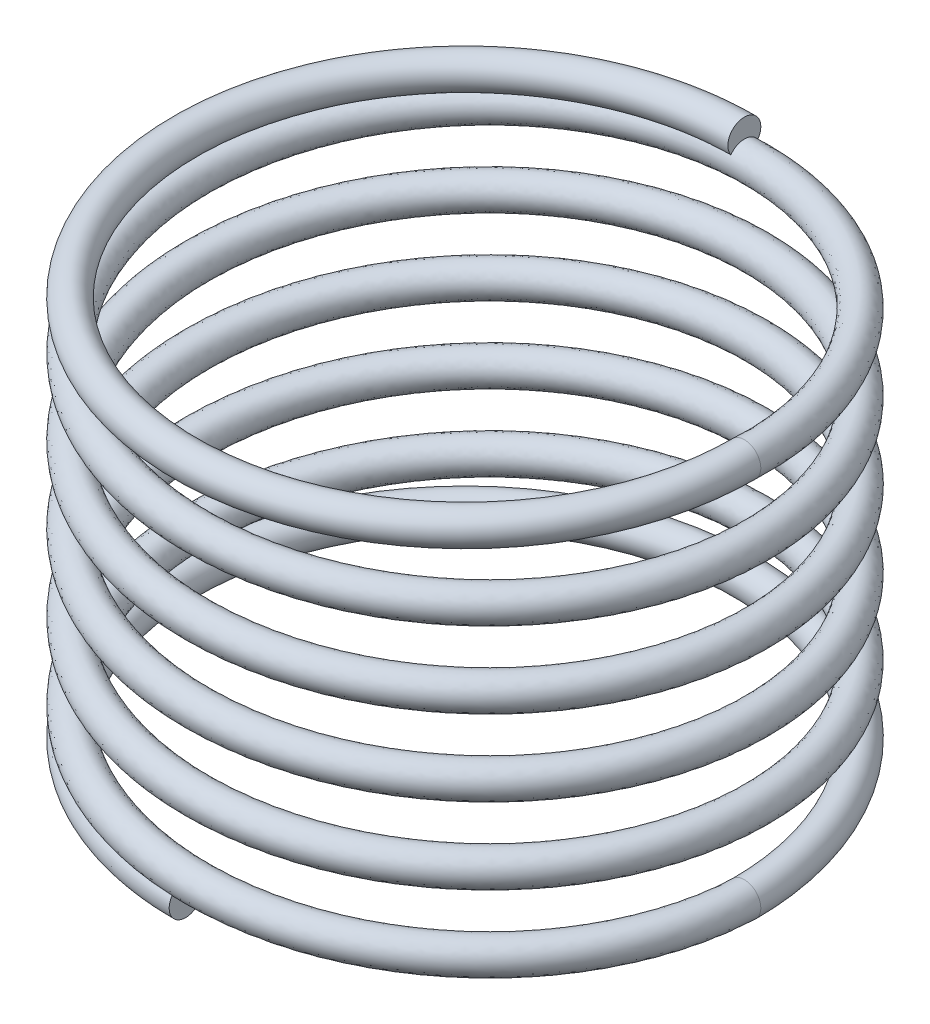
SolidWorks part; units mm, degrees
material "AISI 304"
ref_plane "Front Plane" through (0, 0, 0) normal (0, 0, 1) x (1, 0, 0)
ref_plane "Top Plane" through (0, 0, 0) normal (0, 1, 0) x (1, 0, 0)
ref_plane "Right Plane" through (0, 0, 0) normal (1, 0, 0) x (0, 0, -1)
ref_axis "AXIS" through (0, -20.2934, 0) along (0, 1, 0)
sketch "Sketch1" plane through (0, 0, 0) normal (0, 1, 0) x (1, 0, 0)
  circle A0 centre (0, 0) radius 18.6944
  dimension "D1" = 37.3888
sketch "Sketch2" plane through (0, 0, 0) normal (0, 0, 1) x (1, 0, 0)
  line L0 (18.6944, 0) -> (-18.6944, 0) construction
  circle A0 centre (17.653, 0) radius 1.0414
  point P4 (18.6944, 0)
  dimension "D1" = 2.0828
curve "Helix/Spiral1" pitch 4.8158 height 24.0792 radius 18.6944 left hand yes centre (0, 0, 0) axis (0, 1, 0) start towards (1, 0, 0)
sweep "Sweep1" add profiles "Sketch2" path "Helix/Spiral1"
sketch "Sketch3" plane through (0, 0, 0) normal (0, 0, 1) x (1, 0, 0)
  line L0 (0, 0) -> (0, -14.023) construction
  line L1 (0, -55) -> (0, 55) construction
  circle A1 centre (17.653, 24.0792) radius 1.0414
  circle A2 centre (17.653, 24.0792) radius 1.0414
  dimension "D1" = 0
revolve "Revolve1" add sketch "Sketch3" angle 270 about L0
sketch "Sketch4" plane through (0, 0, 0) normal (0, 0, 1) x (1, 0, 0)
  line L0 (0, 0) -> (0, -9.1384) construction
  circle A1 centre (17.653, 0) radius 1.0414
  circle A2 centre (17.653, 0) radius 1.0414
  dimension "D1" = 0
revolve "Revolve2" add sketch "Sketch4" angle 270 about L0 reverse direction yes
